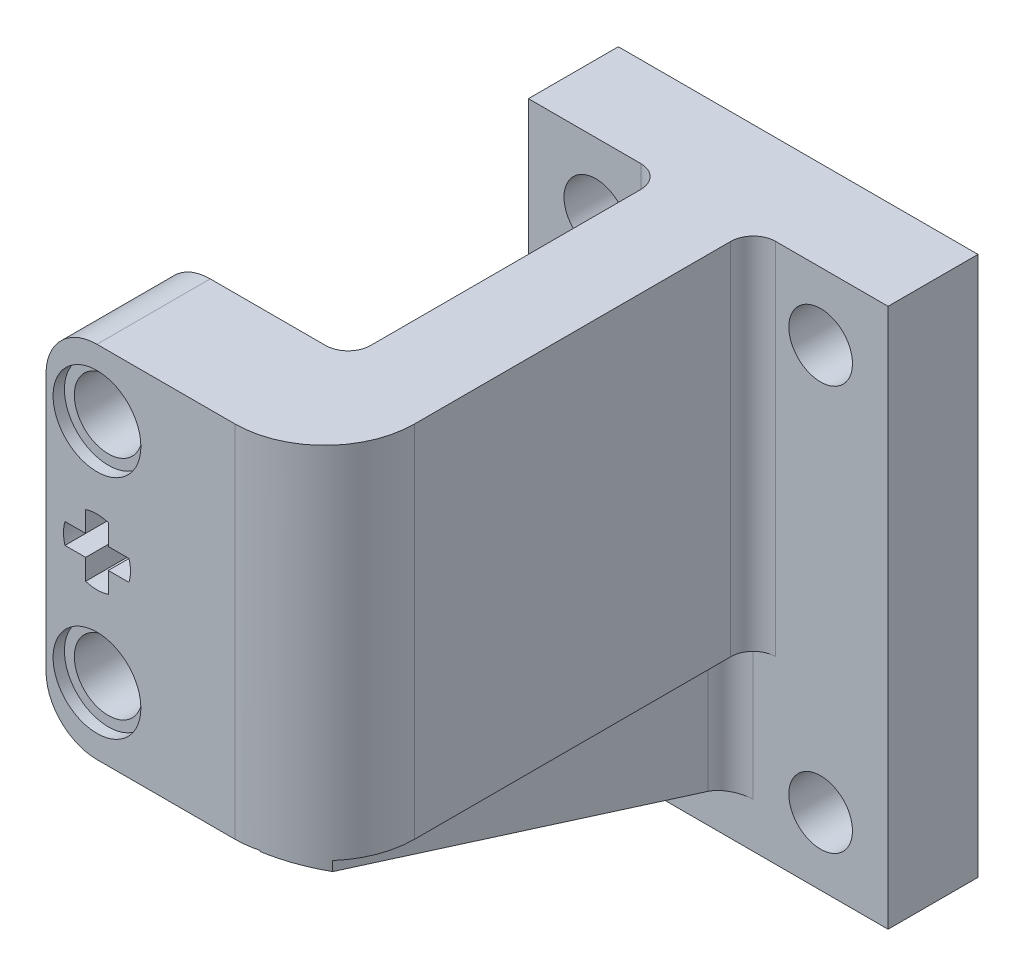
SolidWorks part; units mm, degrees
ref_plane "Front Plane" through (0, 0, 0) normal (0, 0, 1) x (1, 0, 0)
ref_plane "Top Plane" through (0, 0, 0) normal (0, 1, 0) x (1, 0, 0)
ref_plane "Right Plane" through (0, 0, 0) normal (1, 0, 0) x (0, 0, -1)
sketch "Sketch1" plane through (0, 0, 0) normal (0, 1, 0) x (1, 0, 0)
  line L0 (0, 0) -> (0, -22.2563)
  line L1 (0, -22.2563) -> (-13.335, -22.2563)
  line L2 (-13.335, -22.2563) -> (-13.335, -30.2563)
  line L3 (-13.335, -30.2563) -> (6.35, -30.2563)
  line L4 (6.35, -30.2563) -> (6.35, 0)
  line L5 (6.35, 0) -> (15.875, 0)
  line L6 (15.875, 0) -> (15.875, 6.35)
  line L7 (15.875, 6.35) -> (-9.525, 6.35)
  line L8 (-9.525, 6.35) -> (-9.525, 0)
  line L9 (-9.525, 0) -> (0, 0)
  point P3 (-13.335, -26.2563)
  point P12 (3.175, 6.35)
  dimension "D1" = 25.4
  dimension "D2" = 6.35
  dimension "D3" = 6.35
  dimension "D4" = 8
  dimension "D5" = 32.6063
  dimension "D6" = 16.51
extrude "Boss-Extrude1" add sketch "Sketch1" along normal mid plane 25.4 contours L0 L1 L2 L3 L4 L5 L6 L7 L8 L9
sketch "Sketch2" plane through (0, 0, 30.2563) normal (0, 0, 1) x (1, 0, 0)
  line L0 (-10.535, 0.7314) -> (-10.535, 2.1941)
  line L1 (-8.935, 2.1941) -> (-8.935, 0.7314)
  line L2 (-10.535, 0.7314) -> (-8.935, 0.7314) construction
  line L3 (-10.535, 0.7314) -> (-10.535, -0.7314) construction
  line L4 (-10.535, 0.7314) -> (-11.9977, 0.7314)
  line L5 (-11.9977, -0.7314) -> (-10.535, -0.7314)
  line L6 (-10.535, -0.7314) -> (-10.535, -2.1941)
  line L7 (-8.935, -2.1941) -> (-8.935, -0.7314)
  line L8 (-8.935, -0.7314) -> (-7.4723, -0.7314)
  line L9 (-8.935, 0.7314) -> (-7.4723, 0.7314)
  line L10 (-7.4723, 0.7314) -> (-9.5048, 0.7314)
  line L11 (-13.335, 12.7) -> (-13.335, -12.7) construction
  circle A0 centre (-9.735, 0) radius 2.5157 construction
  circle A1 centre (-9.735, 8) radius 3.1
  circle A2 centre (-9.735, -8) radius 3.1
  circle A3 centre (-9.735, 8) radius 2.4
  circle A4 centre (-9.735, -8) radius 2.4
  arc A5 (-10.535, 2.1941) -> (-8.935, 2.1941) centre (-9.735, -0.2798) cw
  arc A6 (-11.9977, 0.7314) -> (-11.9977, -0.7314) centre (-9.5027, 0) ccw
  arc A7 (-10.535, -2.1941) -> (-8.935, -2.1941) centre (-9.735, 0.2798) ccw
  arc A8 (-7.4723, 0.7314) -> (-7.4723, -0.7314) centre (-9.9673, 0) cw
  point P12 (-9.735, 0.7314)
  point P34 (-12.1027, 0)
  point P35 (-9.735, -2.3202)
  dimension "D1" = 6.2
  dimension "D2" = 4.8
  dimension "D7" = 2.6
  dimension "D3" = 8
  dimension "D4" = 8
  dimension "D5" = 1.4627
  dimension "D6" = 1.6
  dimension "D8" = 3.6
extrude "Cut-Extrude1" cut sketch "Sketch2" against normal blind 25.4 contours A8 L9 L1 A5 L0 L4 A6 L5 L6 A7 L7 L8 | A4 | A3 region at (-9.735, 0, 30.2563) region at (-9.735, -8, 30.2563)
extrude "Cut-Extrude2" cut sketch "Sketch2<3>" against normal blind 0.8 contours A1 | A2
sketch "Sketch2<3>" plane through (0, 0, 30.2563) normal (0, 0, 1) x (1, 0, 0) same geometry as "Sketch2"
ref_plane "Plane1" through (0, 0, 26.2563) normal (0, 0, 1) x (1, 0, 0)
mirror "Mirror1" about plane through (0, 0, 26.2563) normal (0, 0, 1) of "Cut-Extrude2"
fillet "Fillet1" radius 3.6 2 edges at (-13.335, -12.7, 26.2563) (-13.335, 12.7, 26.2563)
sketch "Sketch7" plane through (0, 0, -6.35) normal (0, 0, -1) x (-1, 0, 0)
  line L5 (9.525, 12.7) -> (9.525, -12.7) construction
  line L6 (-15.875, 12.7) -> (9.525, 12.7)
  line L8 (-15.875, 12.7) -> (-15.875, -25.4)
  line L9 (-15.875, -25.4) -> (9.525, -25.4)
  line L10 (9.525, 12.7) -> (9.525, -25.4)
  dimension "D1" = 38.1
extrude "Boss-Extrude2" add sketch "Sketch7" against normal up to surface (6.35 mm away) up to face at (11.1125, 0, 0)
hole_wizard "#8 Clearance Hole1" positions "Sketch5" profile "Sketch6" hole size "#8" standard "ANSI Inch" end condition up to next
sketch "Sketch5" plane through (0, 0, -6.35) normal (0, 0, -1) x (-1, 0, 0)
  line L2 (9.525, 12.7) -> (9.525, -25.4) construction
  line L5 (9.525, -25.4) -> (9.525, 12.7) construction
  line L6 (-15.875, 12.7) -> (-15.875, -25.4) construction
  line L7 (-15.875, 12.7) -> (9.525, 12.7) construction
  point P0 (-11.1125, 7.9375)
  point P2 (4.7625, 7.9375)
  point P4 (4.7625, -20.6375)
  point P6 (-11.1125, -20.6375)
  dimension "D1" = 4.7625
  dimension "D2" = 4.7625
  dimension "D3" = 4.7625
  dimension "D4" = 20.6375
sketch "Sketch6" plane through (11.1125, 7.9375, -6.35) normal (1, 0, 0) x (0, 1, 0)
  line L0 (0, 0) -> (0, 6.35)
  line L1 (0, 6.35) -> (2.2479, 6.35)
  line L2 (2.2479, 6.35) -> (2.2479, 0)
  line L5 (2.2479, 0) -> (0, 0)
  line L11 (0, -6.35) -> (0, 107.95) construction
  dimension "Thru Hole Dia." = 4.4958
  dimension "Thru Hole Depth" = 6.35
ref_plane "Plane2" through (3.175, 0, 0) normal (1, 0, 0) x (0, 0, -1)
sketch "Sketch8" plane through (3.175, 0, 0) normal (1, 0, 0) x (0, 0, -1)
  line L0 (0, -22.225) -> (-30.2563, -12.7)
  line L1 (0, 12.7) -> (0, -25.4) construction
  line L2 (-30.2563, -12.7) -> (0, -12.7) construction
  line L3 (-30.2563, -12.7) -> (0, -12.7)
  line L4 (0, -12.7) -> (0, -22.225)
  dimension "D1" = 3.175
extrude "Boss-Extrude3" add sketch "Sketch8" along normal mid plane 3.175 contours L0 L3 L4
fillet "Fillet2" radius 6.35 1 edges at (6.35, 0, 30.2563)
fillet "Fillet3" radius 1.5875 1 edges at (0, 0, 22.2563)
fillet "Fillet4" radius 1.5875 4 edges at (0, 0, 0) (6.35, 0, 0) (1.5875, -17.4625, 0) (4.7625, -17.4625, 0)
